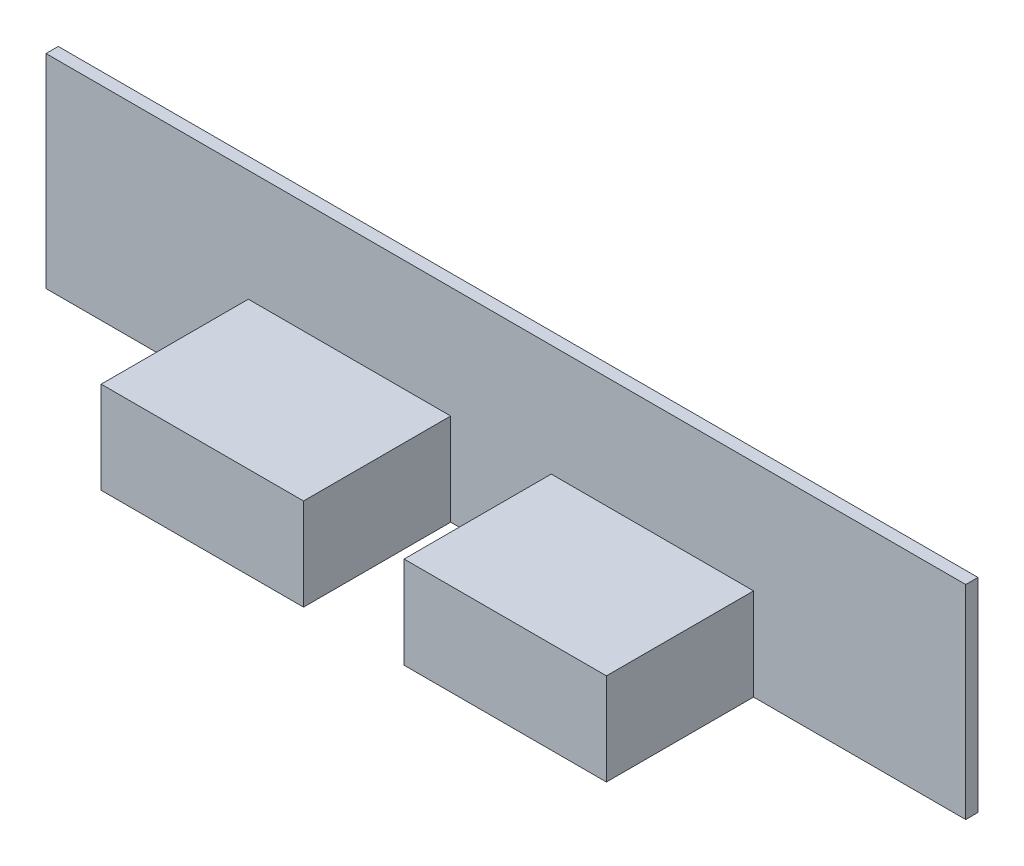
SolidWorks part; units mm, degrees
ref_plane "Front Plane" through (0, 0, 0) normal (0, 0, 1) x (1, 0, 0)
ref_plane "Top Plane" through (0, 0, 0) normal (0, 1, 0) x (1, 0, 0)
ref_plane "Right Plane" through (0, 0, 0) normal (1, 0, 0) x (0, 0, -1)
sketch "Sketch1" plane through (0, 0, 0) normal (0, 0, 1) x (1, 0, 0)
  line L1 (0, 0) -> (190.5, 0)
  line L2 (0, 0) -> (0, 42.164)
  line L3 (0, 42.164) -> (190.5, 42.164)
  line L4 (190.5, 0) -> (190.5, 42.164)
  line L5 (0, 0) -> (190.5, 42.164) construction
  line L6 (0, 42.164) -> (190.5, 0) construction
  line L7 (41.91, 0) -> (83.82, 0)
  line L8 (41.91, 0) -> (41.91, 19.05)
  line L9 (41.91, 19.05) -> (83.82, 19.05)
  line L10 (83.82, 0) -> (83.82, 19.05)
  line L11 (41.91, 0) -> (83.82, 19.05) construction
  line L12 (41.91, 19.05) -> (83.82, 0) construction
  line L13 (104.648, 0) -> (146.558, 0)
  line L14 (104.648, 0) -> (104.648, 19.05)
  line L15 (104.648, 19.05) -> (146.558, 19.05)
  line L16 (146.558, 0) -> (146.558, 19.05)
  line L17 (104.648, 0) -> (146.558, 19.05) construction
  line L18 (104.648, 19.05) -> (146.558, 0) construction
  point P4 (95.25, 21.082)
  point P10 (62.865, 9.525)
  point P15 (125.603, 9.525)
  dimension "D1" = 190.5
  dimension "D2" = 42.164
  dimension "D3" = 41.91
  dimension "D4" = 41.91
  dimension "D5" = 19.05
  dimension "D6" = 20.828
extrude "Boss-Extrude1" add sketch "Sketch1" against normal blind 2.54 contours L16 L1 L4 L3 L2 L8 L9 L10 L14 L15 | L1 L10 L9 L8 | L1 L16 L15 L14 region at (95.5021, 23.9495, 0) region at (62.865, 9.525, 0) region at (125.603, 9.525, 0)
extrude "Boss-Extrude2" add sketch "Sketch1<3>" along normal blind 30.48 contours L1 L10 L9 L8 | L1 L16 L15 L14 region at (62.865, 9.525, 0) region at (125.603, 9.525, 0)
sketch "Sketch1<3>" plane through (0, 0, 0) normal (0, 0, 1) x (1, 0, 0) same geometry as "Sketch1"
